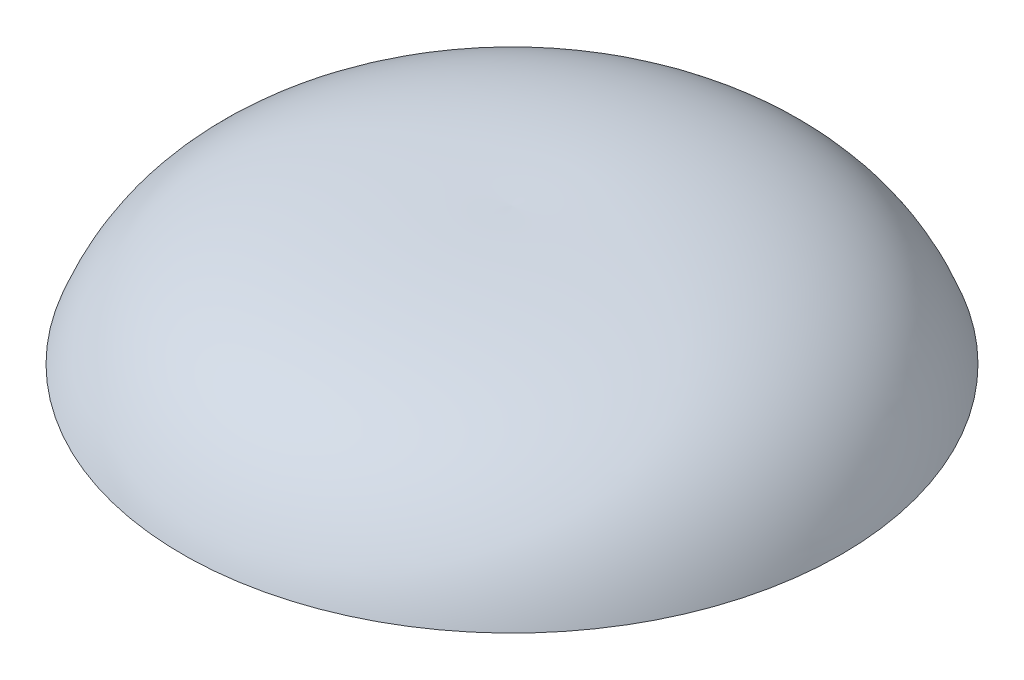
SolidWorks part; units mm, degrees
ref_plane "Front Plane" through (0, 0, 0) normal (0, 0, 1) x (1, 0, 0)
ref_plane "Top Plane" through (0, 0, 0) normal (0, 1, 0) x (1, 0, 0)
ref_plane "Right Plane" through (0, 0, 0) normal (1, 0, 0) x (0, 0, -1)
sketch "Sketch1" plane through (0, 0, 0) normal (0, 0, 1) x (1, 0, 0)
  line L0 (0, 0) -> (12.7, 0)
  line L1 (0, 0) -> (0, -2.54)
  line L2 (0, -2.54) -> (-2.54, -2.54)
  line L3 (-2.54, -2.54) -> (-2.54, 0)
  line L4 (-2.54, 0) -> (-2.54, 6.35)
  line L5 (-2.54, 6.35) -> (-2.54, 8.9499) construction
  spline S0 degree 3 poles (-2.54, 6.35) (5.7374, 6.6484) (10.8169, 5.1774) (12.7, 0) knots 0 0 0 0 1 1 1 1
  dimension "D1" = 12.7
  dimension "D2" = 2.54
  dimension "D3" = 2.54
  dimension "D4" = 2.54
  dimension "D5" = 6.35
ref_axis "Axis1" through (-2.54, 6.35, 0) along (0, 1, 0)
revolve "Revolve1" add sketch "Sketch1" angle 360 about L5
